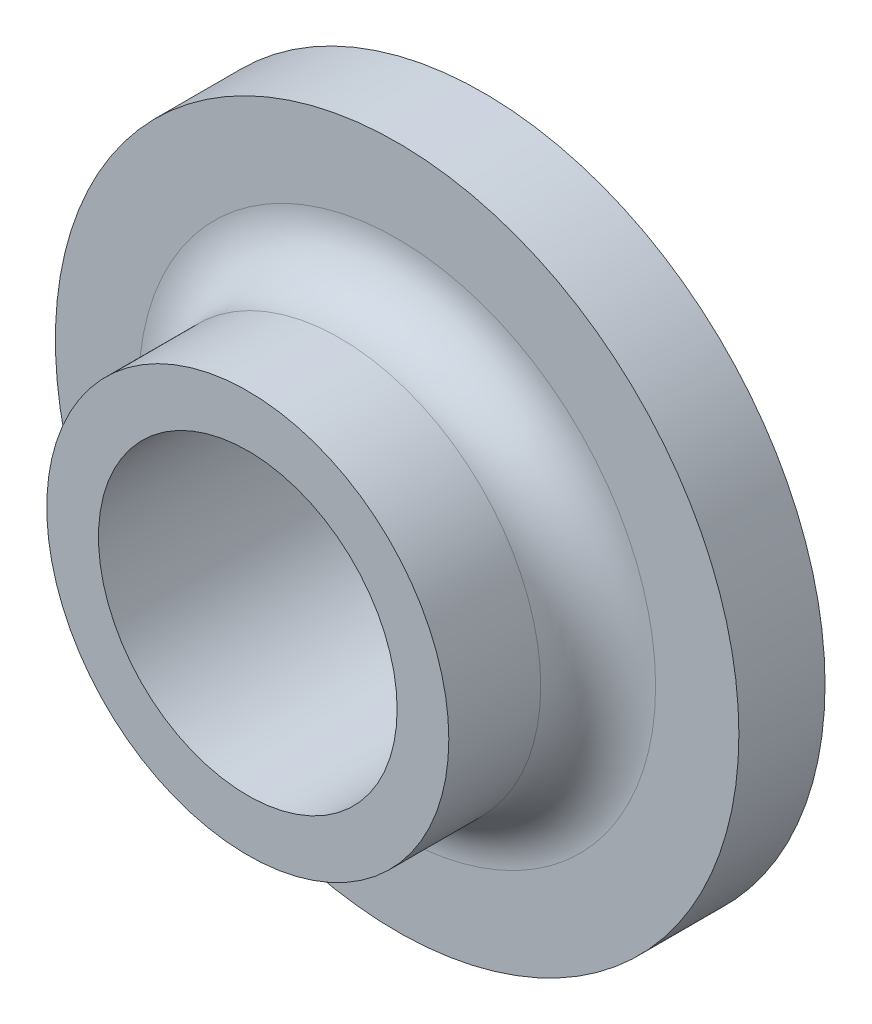
SolidWorks part; units mm, degrees
ref_plane "前视基准面" through (0, 0, 0) normal (0, 0, 1) x (1, 0, 0)
ref_plane "上视基准面" through (0, 0, 0) normal (0, 1, 0) x (1, 0, 0)
ref_plane "右视基准面" through (0, 0, 0) normal (1, 0, 0) x (0, 0, -1)
other "Configuration Table"
sketch "草图1" plane through (0, 0, 0) normal (0, 0, 1) x (1, 0, 0)
  circle A0 centre (0, 0) radius 5.95
  circle A1 centre (0, 0) radius 3.5
  dimension "D1" = 11.9
  dimension "D2" = 7
extrude "凸台-拉伸1" add sketch "草图1" along normal blind 1.5
extrude "凸台-拉伸2" add sketch "草图1<2>" along normal blind 4.1 contours A1 region at (0, 0, 0)
sketch "草图1<2>" plane through (0, 0, 0) normal (0, 0, 1) x (1, 0, 0) same geometry as "草图1"
sketch "草图2" plane through (0, 0, 0) normal (0, 0, 1) x (1, 0, 0)
  circle A0 centre (0, 0) radius 2.6
  dimension "D1" = 5.2
extrude "切除-拉伸1" cut sketch "草图2" along normal through all
fillet "圆角1" radius 1 1 edges at (3.5, 0, 1.5)
